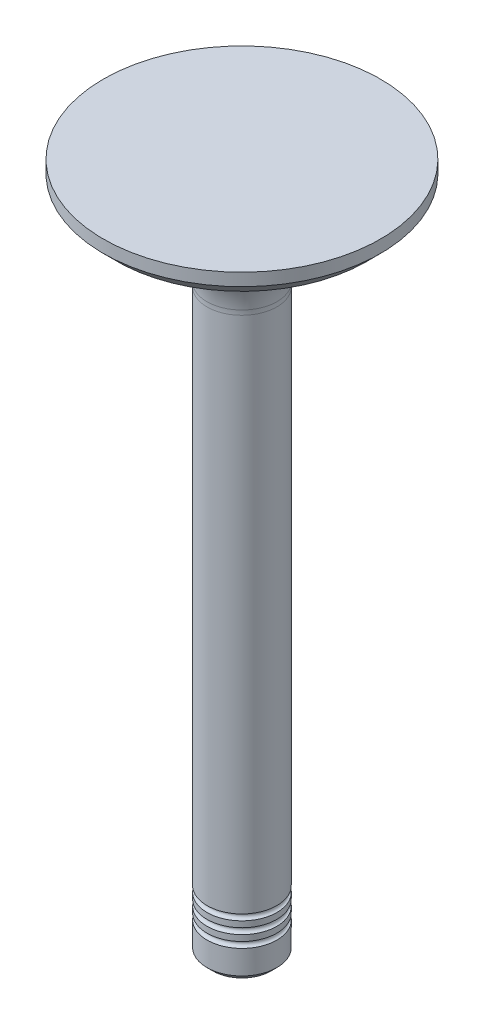
SolidWorks part; units mm, degrees
material "21-2N"
ref_plane "Front Plane" through (0, 0, 0) normal (0, 0, 1) x (1, 0, 0)
ref_plane "Top Plane" through (0, 0, 0) normal (0, 1, 0) x (1, 0, 0)
ref_plane "Right Plane" through (0, 0, 0) normal (1, 0, 0) x (0, 0, -1)
sketch "Sketch1" plane through (0, 0, 0) normal (0, 0, 1) x (1, 0, 0)
  line L0 (0, 105.7218) -> (0, -9.6782) construction
  line L1 (0, 105.7218) -> (-23.22, 105.7218)
  line L2 (-23.22, 105.7218) -> (-23.22, 103.6218)
  line L3 (-23.22, 103.6218) -> (-20.898, 101.2998)
  line L4 (0, 105.7218) -> (0, -9.6782)
  line L5 (-5.85, 87.4698) -> (-5.85, -9.6782)
  line L6 (-5.85, -9.6782) -> (0, -9.6782)
  arc A0 (-20.898, 101.2998) -> (-5.85, 87.4698) centre (-20.3114, 86.8364) cw
  dimension "D2" = 23.22
  dimension "D3" = 2.1
  dimension "D4" = 45
  dimension "D1" = 5.85
  dimension "D6" = 115.4
  dimension "D5" = 2.322
  dimension "D8" = 16.152
revolve "Revolve1" add sketch "Sketch1" angle 360 about L0
fillet "Fillet1" radius 10 1 edges at (-5.85, 87.4698, 0)
chamfer "Chamfer1" distance 1 angle 45 1 edges at (-5.85, -9.6782, 0)
sketch "Sketch2" plane through (0, 0, 0) normal (1, 0, 0) x (0, 0, -1)
  line L1 (-5.85, 87.1884) -> (-5.85, -8.6782) construction
  line L2 (-7.85, -1.6782) -> (-5.85, -1.6782)
  line L3 (-7.85, -2.6782) -> (-5.85, -2.6782)
  line L4 (0, -8.6782) -> (0, 87.9749) construction
  line L5 (5.85, -8.6782) -> (-5.85, -8.6782) construction
  line L6 (5.881, 87.9749) -> (-5.881, 87.9749) construction
  line L7 (-7.85, -2.6782) -> (-7.85, -1.6782)
  line L8 (-7.85, -4.6782) -> (-5.85, -4.6782)
  line L9 (-7.85, -4.6782) -> (-7.85, -3.6782)
  line L10 (-7.85, -3.6782) -> (-5.85, -3.6782)
  line L12 (-7.85, 0.3218) -> (-5.85, 0.3218)
  line L13 (-7.85, -0.6782) -> (-5.85, -0.6782)
  line L14 (-7.85, -0.6782) -> (-7.85, 0.3218)
  arc A1 (-5.85, -4.6782) -> (-5.85, -3.6782) centre (-5.85, -4.1782) ccw
  arc A2 (-5.85, -2.6782) -> (-5.85, -1.6782) centre (-5.85, -2.1782) ccw
  arc A3 (-5.85, -0.6782) -> (-5.85, 0.3218) centre (-5.85, -0.1782) ccw
  point P10 (-5.805, 17.2218)
  dimension "D1" = 4
  dimension "D2" = 1
  dimension "D3" = 3
  dimension "D5" = 2
  dimension "D6" = 1
revolve "Cut-Revolve1" cut sketch "Sketch2" angle 360 about L4
sketch "Sketch3" plane through (0, 0, 0) normal (0, 0, 1) x (1, 0, 0)
  line L0 (0, 105.7218) -> (0, -4.6075) construction
  line L1 (23.22, 105.7218) -> (-23.22, 105.7218) construction
ref_plane "Mating Plane" through (0, 103.6218, 0) normal (0, 1, 0) x (1, 0, 0)
equation "\"Valve Diameter\"= 46.44mm"
equation "\"Seat Angle Beta\"= 45deg"
equation "\"Seat Diameter\"= 41.796mm"
equation "\"Stem Diameter\"= 11.61mm"
equation "\"Seat Width\"= 2.322mm"
equation "\"Max Lift\"= 16.152mm"
equation "\"Overall Length\"= 115.4mm"
equation "\"Head Thickness\"= 2.1mm"
equation "\"D2@Sketch1\"=\"Valve Diameter\"/2"
equation "\"D3@Sketch1\"=\"Head Thickness\""
equation "\"D4@Sketch1\"=\"Seat Angle Beta\""
equation "\"D1@Sketch1\"=5.85"
equation "\"D6@Sketch1\"=\"Overall Length\""
equation "\"D5@Sketch1\"=\"Seat Width\""
equation "\"D8@Sketch1\"=\"Max Lift\""
